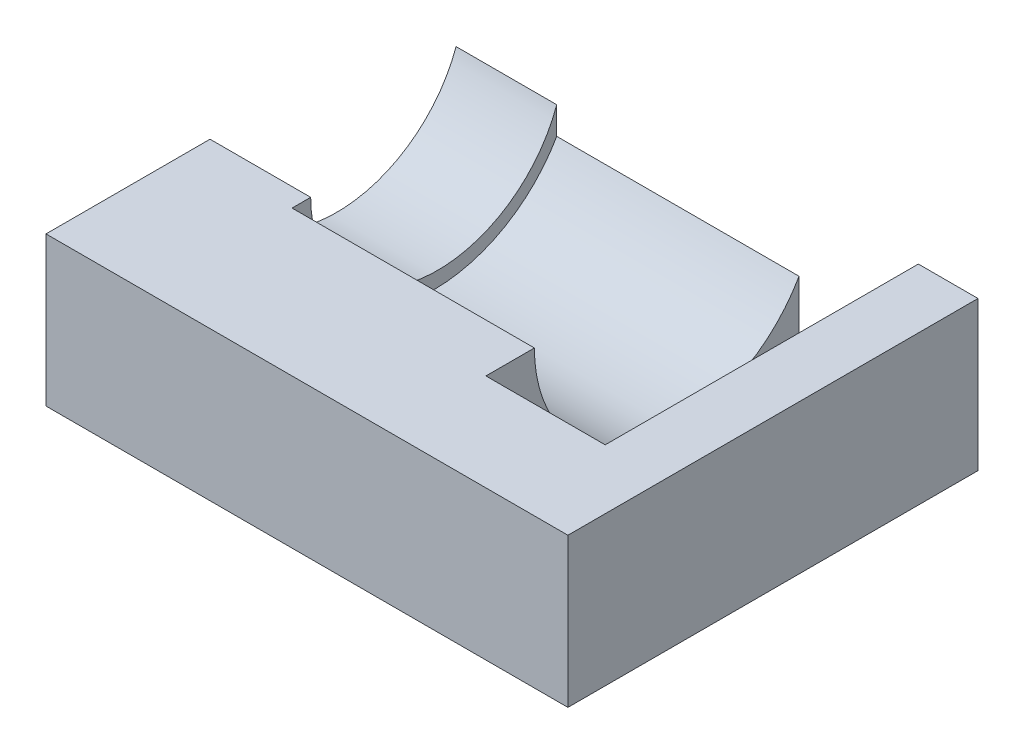
SolidWorks part; units mm, degrees
ref_plane "Front Plane" through (0, 0, 0) normal (0, 0, 1) x (1, 0, 0)
ref_plane "Top Plane" through (0, 0, 0) normal (0, 1, 0) x (1, 0, 0)
ref_plane "Right Plane" through (0, 0, 0) normal (1, 0, 0) x (0, 0, -1)
sketch "Sketch1" plane through (0, 0, 0) normal (0, 1, 0) x (1, 0, 0)
  line L1 (0, 0) -> (70, 0)
  line L2 (0, 0) -> (0, -55)
  line L3 (0, -55) -> (70, -55)
  line L4 (70, 0) -> (70, -55)
  dimension "D1" = 55
  dimension "D2" = 70
extrude "Boss-Extrude1" add sketch "Sketch1" along normal blind 20 contours L1 L4 L3 L2
ref_plane "Plane1" through (62, 0, 0) normal (1, 0, 0) x (0, 0, -1)
sketch "Sketch2" plane through (62, 0, 0) normal (1, 0, 0) x (0, 0, -1)
  line L0 (0, 0) -> (-55, 0) construction
  line L2 (-55, 20) -> (-55, 0) construction
  circle A0 centre (-16, 20) radius 26
  dimension "D1" = 52
  dimension "D2" = 20
  dimension "D3" = 39
extrude "Cut-Extrude1" cut sketch "Sketch2" against normal blind 16 contours A0
sketch "Sketch3" plane through (0, 0, 0) normal (-1, 0, 0) x (0, 0, 1)
  line L0 (0, 20) -> (55, 20) construction
  line L1 (55, 20) -> (55, 0) construction
  circle A0 centre (16, 20) radius 17
  dimension "D1" = 34
  dimension "D2" = 39
extrude "Cut-Extrude2" cut sketch "Sketch3" against normal blind 13.5 contours A0
sketch "Sketch5" plane through (13.5, 0, 0) normal (-1, 0, 0) x (0, 0, 1)
  line L0 (0, 20) -> (33, 20) construction
  circle A0 centre (16.5, 20) radius 19
  dimension "D1" = 38
extrude "Cut-Extrude3" cut sketch "Sketch5" against normal up to surface (32.5 mm away) up to face at (46, 9.7383, 19.2108)
